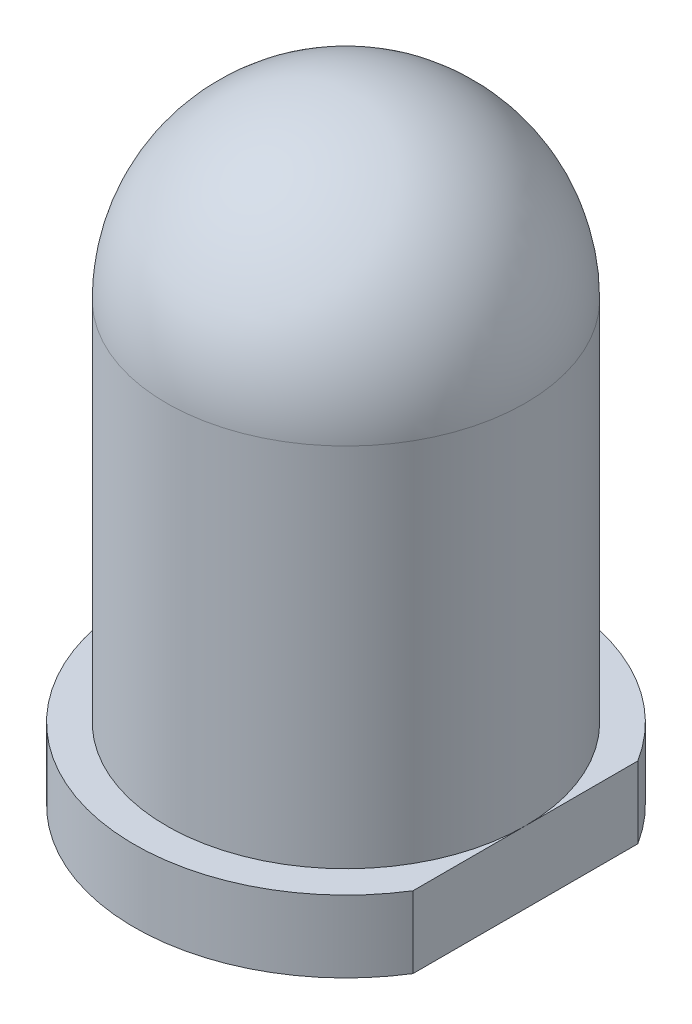
SolidWorks part; units mm, degrees
ref_plane "Front Plane" through (0, 0, 0) normal (0, 0, 1) x (1, 0, 0)
ref_plane "Top Plane" through (0, 0, 0) normal (0, 1, 0) x (1, 0, 0)
ref_plane "Right Plane" through (0, 0, 0) normal (1, 0, 0) x (0, 0, -1)
sketch "Body Profile" plane through (0, 0, 0) normal (0, 0, 1) x (1, 0, 0)
  line L0 (0, -170.0139) -> (0, 8330.6815) construction
  line L1 (2.5, 5.1) -> (2.5, 0)
  line L2 (0, 0) -> (2.5, 0)
  line L3 (0, 7.6) -> (0, 0)
  line L4 (-2.5, 5.1) -> (-2.5, 0) construction
  line L5 (0, 0) -> (-2.5, 0) construction
  arc A0 (2.5, 5.1) -> (0, 7.6) centre (0, 5.1) ccw
  arc A1 (0, 7.6) -> (-2.5, 5.1) centre (0, 5.1) ccw construction
  dimension "Height" = 7.6
  dimension "Diameter" = 5
revolve "Body" add sketch "Body Profile" angle 360 about L0
sketch "Flange Outline" plane through (0, 0, 0) normal (0, -1, 0) x (1, 0, 0)
  line L0 (2.5, -1.566) -> (2.5, 1.566)
  arc A0 (2.5, 1.566) -> (2.5, -1.566) centre (0, 0) ccw
  circle A2 centre (0, 0) radius 2.5 construction
  dimension "Diameter" = 5.9
extrude "Flange" add sketch "Flange Outline" along normal blind 1
ref_axis "Center line" through (0, 5.1, 0) along (0, -1, 0)
